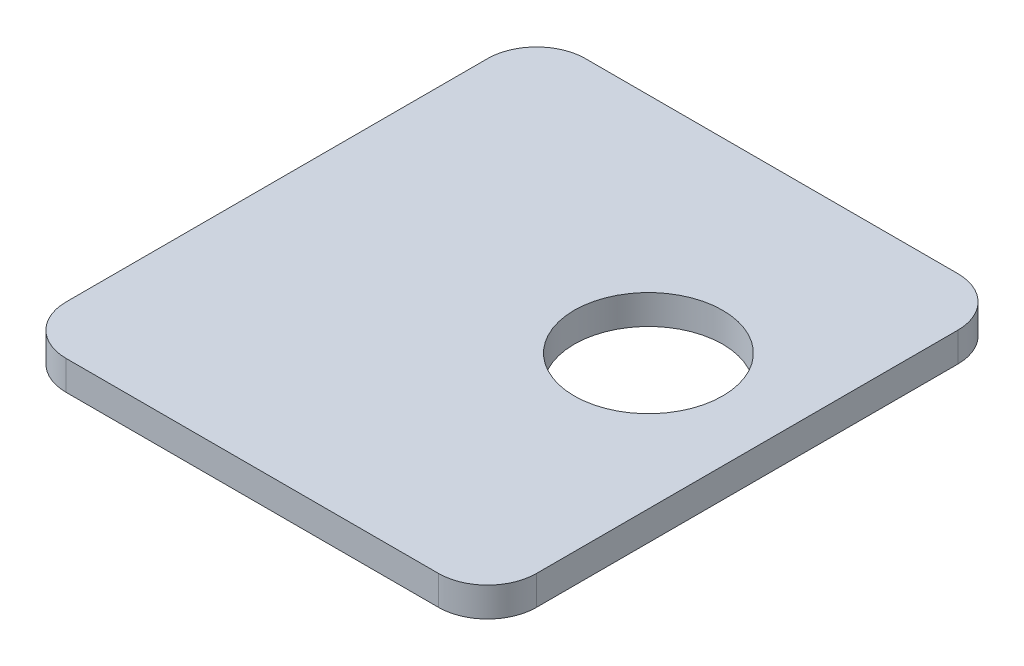
SolidWorks part; units mm, degrees
material "Acrylic (Medium-high impact)"
ref_plane "Front Plane" through (0, 0, 0) normal (0, 0, 1) x (1, 0, 0)
ref_plane "Top Plane" through (0, 0, 0) normal (0, 1, 0) x (1, 0, 0)
ref_plane "Right Plane" through (0, 0, 0) normal (1, 0, 0) x (0, 0, -1)
sketch "Sketch1" plane through (0, 0, 0) normal (0, 1, 0) x (1, 0, 0)
  line L1 (-19.4223, 32.2067) -> (18.5777, 32.2067)
  line L2 (-24.4223, 27.2067) -> (-24.4223, -15.7933)
  line L3 (-19.4223, -20.7933) -> (18.5777, -20.7933)
  line L4 (23.5777, 27.2067) -> (23.5777, -15.7933)
  arc A0 (-24.4223, 27.2067) -> (-19.4223, 32.2067) centre (-19.4223, 27.2067) cw
  arc A1 (-24.4223, -15.7933) -> (-19.4223, -20.7933) centre (-19.4223, -15.7933) ccw
  arc A2 (23.5777, -15.7933) -> (18.5777, -20.7933) centre (18.5777, -15.7933) cw
  arc A3 (23.5777, 27.2067) -> (18.5777, 32.2067) centre (18.5777, 27.2067) ccw
  circle A6 centre (9.8184, 9.3921) radius 7.575
  circle A7 centre (9.8184, 9.3921) radius 7.575
  point P6 (-24.4223, 32.2067)
  point P9 (-24.4223, -20.7933)
  point P14 (23.5777, 32.2067)
  dimension "D3" = 5
  dimension "D1" = 53
  dimension "D2" = 48
  dimension "D4" = 0.25
extrude "Boss-Extrude1" add sketch "Sketch1" along normal blind 3
